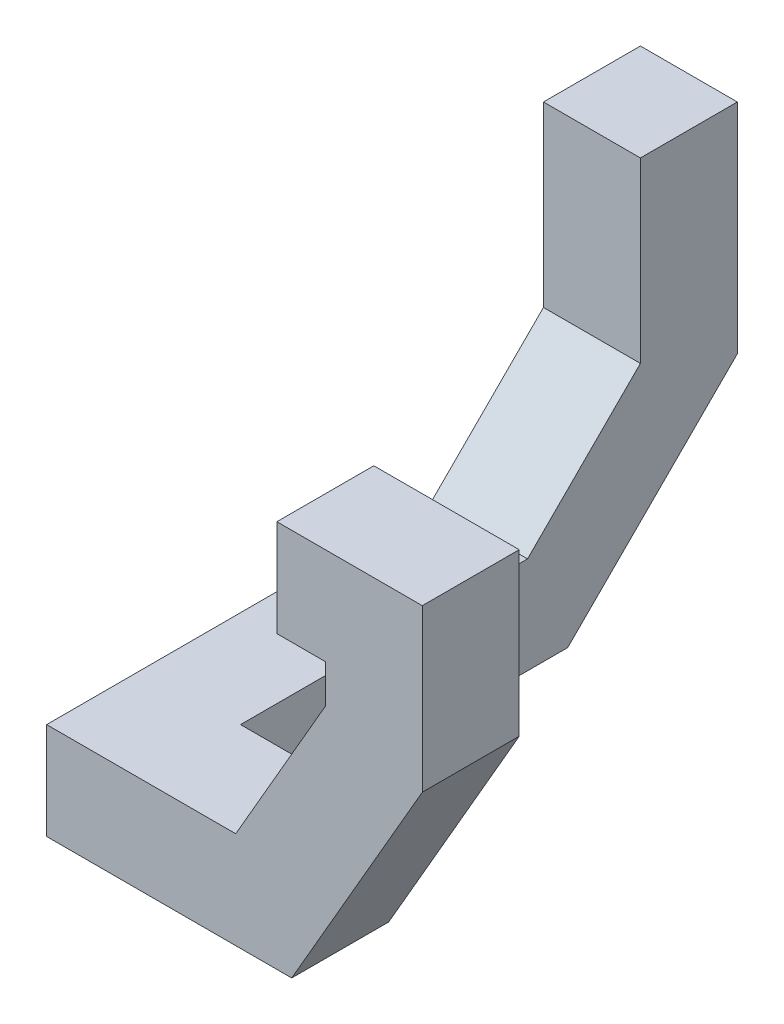
SolidWorks part; units mm, degrees
ref_plane "Front Plane" through (0, 0, 0) normal (0, 0, 1) x (1, 0, 0)
ref_plane "Top Plane" through (0, 0, 0) normal (0, 1, 0) x (1, 0, 0)
ref_plane "Right Plane" through (0, 0, 0) normal (1, 0, 0) x (0, 0, -1)
ref_axis "Z" through (0, 0, 49.875) along (0, 0, -1)
sketch "Sketch1" plane through (0, 0, 0) normal (1, 0, 0) x (0, 0, -1)
  line L0 (-8, 4) -> (0, 4)
  line L1 (0, 4) -> (0, -14)
  line L2 (0, -14) -> (-14, -28)
  line L3 (-14, -28) -> (-45, -28)
  line L4 (-45, -28) -> (-45, -20)
  line L5 (-45, -20) -> (-17.3137, -20)
  line L6 (-17.3137, -20) -> (-8, -10.6863)
  line L7 (-8, -10.6863) -> (-8, 4)
  line L8 (-13.4134, -16.0997) -> (-7.7566, -21.7566) construction
  point P10 (-12.4478, -15.7143)
  point P11 (0, 0)
  point P12 (0, 0)
  point P13 (-8, -5.5266)
  point P15 (-8, 4.933)
  point P16 (-7.7566, -11.6782)
  dimension "D1" = 8
  dimension "D2" = 45
  dimension "D3" = 28
  dimension "D4" = 4
  dimension "D5" = 135
  dimension "D6" = 14
extrude "Boss-Extrude1" add sketch "Sketch1" along normal blind 4 and the other way blind 4
sketch "Sketch2" plane through (0, 0, 45) normal (0, 0, 1) x (1, 0, 0)
  line L0 (5, -20) -> (11.604, -20)
  line L1 (11.604, -20) -> (19, -7.1897)
  line L2 (19, -7.1897) -> (19, -4)
  line L3 (19, -4) -> (15, -4)
  line L4 (15, -4) -> (15, 4)
  line L5 (15, 4) -> (27, 4)
  line L6 (27, 4) -> (27, -9.3333)
  line L7 (27, -9.3333) -> (16.2228, -28)
  line L8 (16.2228, -28) -> (5, -28)
  line L9 (5, -28) -> (-4, -28)
  line L10 (-4, -28) -> (-4, -20)
  line L11 (-4, -20) -> (5, -20)
  line L12 (4, -20) -> (-4, -20) construction
  line L13 (4, -28) -> (-4, -28) construction
  line L14 (-4, -20) -> (-4, -28) construction
  line L15 (16.2847, -11.8928) -> (23.2129, -15.8928) construction
  line L16 (19, -4) -> (27, -4) construction
  line L17 (0, 0) -> (15, 0) construction
  circle A0 centre (0, 0) radius 14 construction
  dimension "D5" = 28
  dimension "D1" = 15
  dimension "D3" = 18.6667
  dimension "D4" = 120
extrude "Boss-Extrude2" add sketch "Sketch2" along normal blind 4 and the other way blind 4
ref_axis "Axis2" through (-23.0447, 0, 45) along (1, 0, 0)
equation "\"rbracket-width\"= 8"
equation "\"D1@Boss-Extrude1\"=\"rbracket-width\"/2"
equation "\"D2@Boss-Extrude1\"=\"rbracket-width\"/2"
equation "\"EyeCaptureRadius\"= ( \"EyeDiameter\" + \"EyeClearance\" ) / 2"
equation "\"D1@Sketch2\"=\"EyeCaptureRadius\""
equation "\"D1@Boss-Extrude2\"=\"rbracket-width\"/2"
equation "\"D2@Boss-Extrude2\"=\"rbracket-width\"/2"
equation "\"rbracket_planetocenterline_dist\" = \"BasePlaneDistance\""
equation "\"D2@Sketch1\"=\"rbracket_planetocenterline_dist\""
equation "\"EyeDiameter\" = 28"
equation "\"BasePlaneDistance\" = 45"
equation "\"EyeClearance\" = 2"
equation "\"D1@Sketch1\"=\"rbracket-width\""
equation "\"D3@Sketch1\"=\"EyeDiameter\""
equation "\"D4@Sketch1\"=\"rbracket-width\"/2"
equation "\"D6@Sketch1\"=\"EyeDiameter\"/2"
equation "\"D2@Sketch2\"=\"rbracket-width\"/2"
equation "\"D3@Sketch2\"=\"EyeDiameter\"*2/3"
equation "\"D5@Sketch2\"=\"EyeDiameter\""
